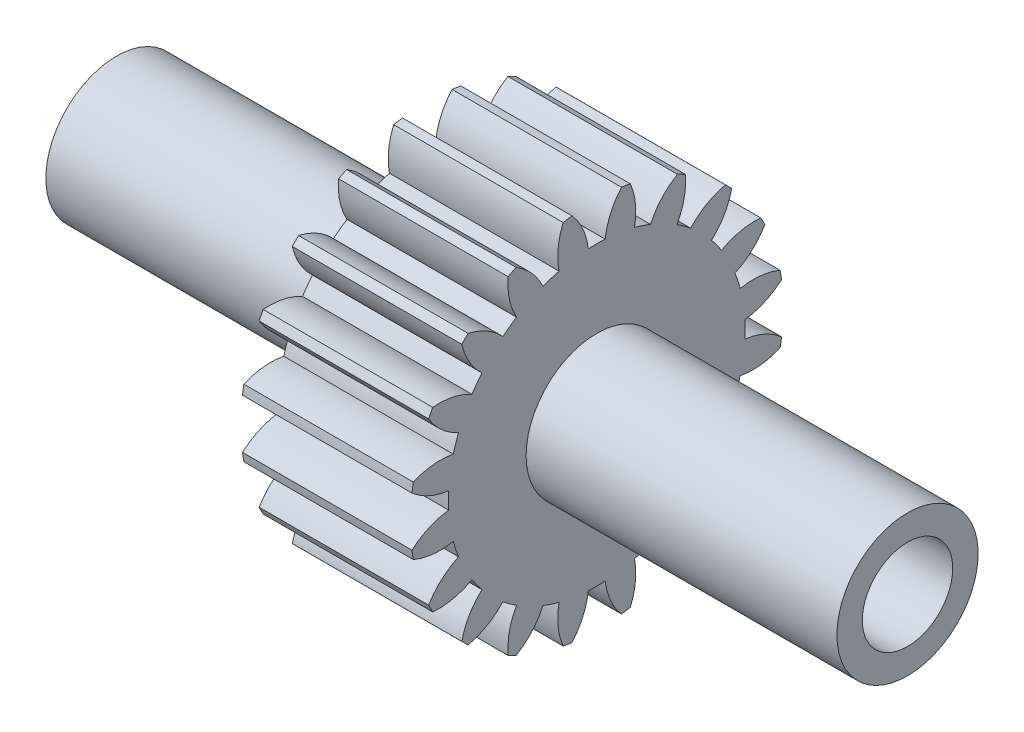
SolidWorks part; units mm, degrees
ref_plane "Plane1" through (0, 0, 0) normal (0, 0, 1) x (1, 0, 0)
ref_plane "Plane2" through (0, 0, 0) normal (0, 1, 0) x (1, 0, 0)
ref_plane "Plane3" through (0, 0, 0) normal (1, 0, 0) x (0, 0, -1)
other "Configuration Table"
sketch "HoldingSke" plane through (0, 0, 0) normal (0, 1, 0) x (1, 0, 0)
  line L0 (0, 0) -> (0.6265, -0.228)
  line L1 (-15, 0) -> (100, 0) construction
  line L2 (0, 0) -> (-2.1039, 2.3779)
  line L3 (0, 0) -> (-11.863, 4.5341)
  line L4 (0, 0) -> (8.1152, 2.9537)
  line L5 (0, 0) -> (-65.5867, -24.4619)
  line L6 (0, 0) -> (-12.4344, -8.3896)
  line L7 (-2.1039, 2.3779) -> (12.9636, 70.7371)
  line L8 (-76.2, 54.61) -> (-74.8, 54.61)
  line L9 (-71.009, 38.7566) -> (-53.1078, 45.2721)
  line L10 (-76.2, 71.12) -> (104.1128, 71.12)
  line L11 (0, 0) -> (-15, 0)
  line L12 (-76.2, 101.6) -> (-76.147, 101.6)
  line L13 (24.9733, 27.94) -> (52.9518, 28.4284)
  line L14 (24.9733, 27.94) -> (24.9743, 27.94)
  line L15 (24.9733, 27.94) -> (100.4006, 29.5858)
  line L16 (-63.627, -1.5) -> (-12.827, -1.5)
  circle A0 centre (0, 0) radius 4
  circle A1 centre (0, 0) radius 6.25
  circle A2 centre (0, 0) radius 6.25
  circle A3 centre (0, 0) radius 4
  dimension "Num_teeth" = 20
  dimension "Pitch_radius" = 180.3128
  dimension "Width" = 15
  dimension "Thickness" = 15
sketch "BasProSke" plane through (0, 0, 0) normal (0, 1, 0) x (1, 0, 0)
  line L0 (-10, 0) -> (60, 0) construction
  line L1 (0, 0) -> (0, 16.5)
  line L2 (0, 0) -> (15, 0)
  line L3 (15, 0) -> (15, 16.5)
  line L4 (15, 16.5) -> (0, 16.5)
  dimension "Thickness" = 15
  dimension "Diameter" = 33
revolve "Base-Revolve" add sketch "BasProSke" angle 360 about L0
sketch "TooCutSke" plane through (0, 0, 0) normal (1, 0, 0) x (0, 0, -1)
  line L1 (0, 0) -> (0, 107) construction
  line L2 (0, 0) -> (-1.2696, 14.9462) construction
  line L3 (0, 0) -> (-4.6808, 29.5532) construction
  line L4 (-1.2696, 14.9462) -> (-2.3404, 14.7766) construction
  arc A0 (0.7438, 13.1029) -> (-0.7438, 13.1029) centre (0, 0) ccw
  arc A1 (2.21, 16.377) -> (-2.21, 16.377) centre (0, 0) ccw
  circle A2 centre (0, 0) radius 15 construction
  circle A3 centre (0, 0) radius 14.0954 construction
  arc A4 (-0.7438, 13.1029) -> (-2.21, 16.377) centre (-6.7025, 12.3999) ccw
  arc A5 (2.21, 16.377) -> (0.7438, 13.1029) centre (6.7025, 12.3999) ccw
extrude "ToothCut" cut sketch "TooCutSke" along normal through all
fillet "Breaks" [suppressed] radius 0.03 tangent propagation no
fillet "RootFillets" [suppressed] radius 0.376
pattern_circular "TeethCuts" count 20 every 18 about axis through (-10, 0, 0) along (1, 0, 0) of "ToothCut", "RootFillets", "Breaks"
sketch "HubNeaOneSke" plane through (0, 0, 0) normal (-1, 0, 0) x (0, 0, 1)
  circle A0 centre (0, 0) radius 6.25
  dimension "Diameter" = 12.5
extrude "HubNearOne" [suppressed] add sketch "HubNeaOneSke" along normal blind 55.0001
sketch "HubNeaBotSke" plane through (0, 0, 0) normal (-1, 0, 0) x (0, 0, 1)
  circle A0 centre (0, 0) radius 6.25
  dimension "Diameter" = 12.5
extrude "HubNearBoth" add sketch "HubNeaBotSke" along normal blind 27.5
ref_plane "FarPln" through (15, 0, 0) normal (1, 0, 0) x (0, 0, -1)
sketch "HubFarSke" plane through (15, 0, 0) normal (1, 0, 0) x (0, 0, -1)
  circle A0 centre (0, 0) radius 6.25
  dimension "Diameter" = 12.5
extrude "HubFar" add sketch "HubFarSke" along normal blind 27.5
sketch "BorSke" plane through (0, 0, 0) normal (1, 0, 0) x (0, 0, -1)
  circle A0 centre (0, 0) radius 4
  dimension "Diameter" = 8
extrude "Bore" cut sketch "BorSke" along normal mid plane 140.0001
sketch "KeySke" plane through (0, 0, 0) normal (1, 0, 0) x (0, 0, -1)
  line L0 (-1.5, 0) -> (-1.5, 5.4)
  line L1 (-1.5, 5.4) -> (1.5, 5.4)
  line L2 (1.5, 5.4) -> (1.5, 0)
  line L3 (0, 0) -> (0, 34) construction
  line L4 (-1.5, 0) -> (1.5, 0)
  dimension "Width" = 3
extrude "Keyway" [suppressed] cut sketch "KeySke" along normal mid plane 140.0001
pattern_circular "Keyway2" [suppressed] count 2 every 90 about axis through (-10, 0, 0) along (1, 0, 0)
equation "' \"Module@HoldingSke\" = 6.35"
equation "' \"Num_teeth@HoldingSke\" = 12"
equation "' \"Ap@HoldingSke\" =  20"
equation "' \"Ap@HoldingSke\" = 20"
equation "' \"Width@HoldingSke\" = 0.5 * 25.4"
equation "' \"Hub_dia@HoldingSke\"= 1 * 25.4"
equation "' \"Hub_dia@HoldingSke\" = 1 * 25.4"
equation "' \"Overall_len@HoldingSke\" = 1.0 * 25.4"
equation "' \"Bore@HoldingSke\" = 0.75 * 25.4"
equation "' \"T_dim@HoldingSke\" = 0.1 * 25.4"
equation "' \"Width@KeySke\" = 0.25 * 25.4"
equation "' \"Show_teeth@HoldingSke\" = 13"
equation "' \"Backlash@HoldingSke\" = 0.009 * 25.4"
equation "' \"Addendum_fac@HoldingSke\" = 1.0"
equation "' \"Dedendum_fac@HoldingSke\" = 1.25"
equation "' \"Dedendum_add@HoldingSke\" = 0.00005 * 25.4"
equation "' \"Clearance_fac@HoldingSke\" = 0.25"
equation "\"Pitch@HoldingSke\" = 1 / \"Module@HoldingSke\""
equation "\"Overcut_dia@TooCutSke\" = (\"Num_teeth@HoldingSke\" + 2 * \"Addendum_fac@HoldingSke\") / \"Pitch@HoldingSke\" + 0.002 * 25.4"
equation "\"Pitch_dia@TooCutSke\" = \"Num_teeth@HoldingSke\" / \"Pitch@HoldingSke\""
equation "\"Base_dia@TooCutSke\" = \"Num_teeth@HoldingSke\" / \"Pitch@HoldingSke\" * cos((\"Ap@HoldingSke\"  * 3.14159265 / 180))"
equation "\"Root_dia@TooCutSke\" = (\"Num_teeth@HoldingSke\" + 2) / \"Pitch@HoldingSke\" - 2 * (\"Addendum_fac@HoldingSke\" + \"Dedendum_fac@HoldingSke\") / \"Pitch@HoldingSke\" - \"Dedendum_add@HoldingSke\" * 2"
equation "\"Half_ang@TooCutSke\" = 180 / \"Num_teeth@HoldingSke\""
equation "\"Half_CT@TooCutSke\" = \"Num_teeth@HoldingSke\" / \"Pitch@HoldingSke\" * sin((3.14159265 / 2 / \"Num_teeth@HoldingSke\")) / 2 - 7 * \"Backlash@HoldingSke\" / 4"
equation "\"Flank_rad@TooCutSke\" = \"Num_teeth@HoldingSke\" / \"Pitch@HoldingSke\" / 5"
equation "\"Radius@RootFillets\" = \"Clearance_fac@HoldingSke\" / \"Pitch@HoldingSke\" + \"Dedendum_add@HoldingSke\""
equation "\"Break_rad@Breaks\" = 0.02 / \"Pitch@HoldingSke\""
equation "\"Thickness@HoldingSke\" = \"Width@HoldingSke\""
equation "\"OAL@HoldingSke\" = \"Thickness@HoldingSke\""
equation "\"MHD@HoldingSke\" = (\"Num_teeth@HoldingSke\" + 2) / \"Pitch@HoldingSke\" - 2 * (\"Addendum_fac@HoldingSke\" + \"Dedendum_fac@HoldingSke\")  / \"Pitch@HoldingSke\" - \"Dedendum_add@HoldingSke\" * 2"
equation "\"MBD@HoldingSke\" = (\"Num_teeth@HoldingSke\" + 2) / \"Pitch@HoldingSke\" - 2 * (\"Addendum_fac@HoldingSke\" + \"Dedendum_fac@HoldingSke\")  / \"Pitch@HoldingSke\" - \"Dedendum_add@HoldingSke\" * 2 - 0.002 * 25.4"
equation "\"MHD@HoldingSke\" = ((sgn( \"MHD@HoldingSke\" - \"Hub_dia@HoldingSke\" )-1)*( \"MHD@HoldingSke\" - \"Hub_dia@HoldingSke\" ))/-2+ \"Hub_dia@HoldingSke\""
equation "\"MBD@HoldingSke\" = ((sgn( \"MBD@HoldingSke\" - \"Bore@HoldingSke\" )-1)*( \"MBD@HoldingSke\" - \"Bore@HoldingSke\" ))/-2+ \"Bore@HoldingSke\""
equation "\"OAL@HoldingSke\" = ((sgn( \"OAL@HoldingSke\" - \"Overall_len@HoldingSke\" )+1)*( \"OAL@HoldingSke\" - \"Overall_len@HoldingSke\" ))/2 + \"Overall_len@HoldingSke\" + 0.000002 * 25.4"
equation "\"Num_teeth@TeethCuts\" = int( \"Show_teeth@HoldingSke\" ) + 1"
equation "\"Num_teeth@TeethCuts\" = ((sgn( \"Num_teeth@TeethCuts\" - \"Num_teeth@HoldingSke\" )-1)*( \"Num_teeth@TeethCuts\" - \"Num_teeth@HoldingSke\" ))/-2+ \"Num_teeth@HoldingSke\""
equation "\"Num_teeth@TeethCuts\" = ((sgn( \"Num_teeth@TeethCuts\" - 2.0)+1)*( \"Num_teeth@TeethCuts\" - 2.0))/2 +2.0"
equation "\"Angle@TeethCuts\" = 360.0 / \"Num_teeth@HoldingSke\""
equation "\"Diameter@BasProSke\" = (\"Num_teeth@HoldingSke\" + 2 * \"Addendum_fac@HoldingSke\") / \"Pitch@HoldingSke\""
equation "\"Thickness@BasProSke\"  = \"Thickness@HoldingSke\""
equation "' \"Fillet_rad@BasProSke\" =  \"Thickness@HoldingSke\" * 0.05"
equation "' \"Fillet_rad@BasProSke\" = \"Thickness@HoldingSke\" * 0.05"
equation "\"MHD@HoldingSke\" = ((sgn( \"MHD@HoldingSke\" - \"Root_dia@TooCutSke\" )-1)*( \"MHD@HoldingSke\" - \"Root_dia@TooCutSke\" ))/-2+ \"Root_dia@TooCutSke\""
equation "\"Diameter@HubNeaOneSke\" = \"MHD@HoldingSke\""
equation "\"Length@HubNearOne\" = \"OAL@HoldingSke\" - \"Thickness@BasProSke\""
equation "\"Diameter@HubNeaBotSke\" = \"MHD@HoldingSke\""
equation "\"Length@HubNearBoth\" = ( \"OAL@HoldingSke\" - \"Thickness@BasProSke\" ) / 2.0"
equation "\"Thickness@FarPln\" = \"Thickness@BasProSke\""
equation "\"Diameter@HubFarSke\" = \"MHD@HoldingSke\""
equation "\"Length@HubFar\" = ( \"OAL@HoldingSke\" - \"Thickness@BasProSke\" ) / 2.0"
equation "\"Diameter@BorSke\" = \"MBD@HoldingSke\""
equation "\"D1@Bore\" = \"OAL@HoldingSke\" * 2.0"
equation "\"D1@Keyway\" = \"OAL@HoldingSke\" * 2.0"
equation "\"Offset@KeySke\" = \"T_dim@HoldingSke\" + \"MBD@HoldingSke\" / 2.0"
